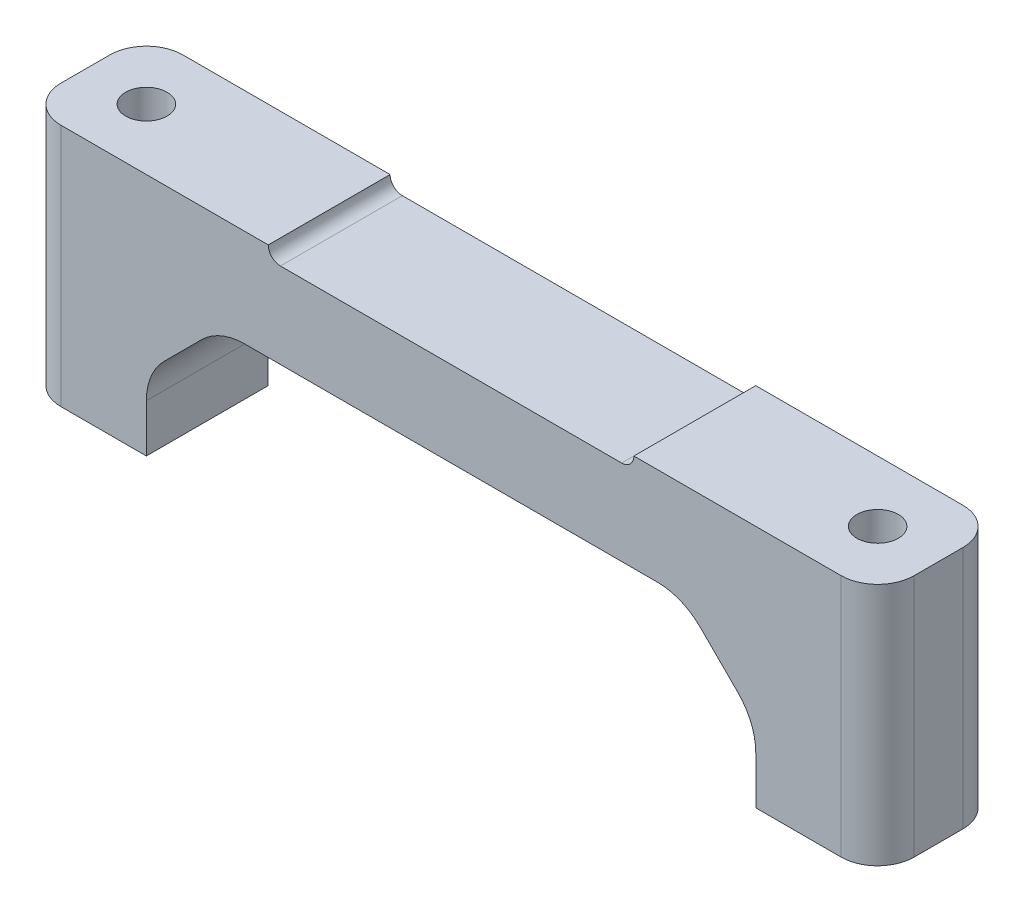
SolidWorks part; units mm, degrees
ref_plane "前视" through (0, 0, 0) normal (0, 0, 1) x (1, 0, 0)
ref_plane "上视" through (0, 0, 0) normal (0, 1, 0) x (1, 0, 0)
ref_plane "右视" through (0, 0, 0) normal (1, 0, 0) x (0, 0, -1)
sketch "草图1" plane through (0, 0, 0) normal (0, 1, 0) x (1, 0, 0)
  line L1 (-35, -5) -> (35, -5)
  line L2 (-35, -5) -> (-35, 5)
  line L3 (-35, 5) -> (35, 5)
  line L4 (35, -5) -> (35, 5)
  line L5 (-35, -5) -> (35, 5) construction
  line L6 (-35, 5) -> (35, -5) construction
  point P0 (0, 0)
  dimension "D1" = 70
  dimension "D2" = 10
extrude "凸台-拉伸1" add sketch "草图1" along normal blind 20
sketch "草图2" plane through (0, 20, 0) normal (0, 1, 0) x (1, 0, 0)
  line L0 (-35, 5) -> (-35, -5) construction
  line L1 (0, 3.006) -> (0, -1.9506) construction
  circle A0 centre (-30, 0) radius 1.7
  circle A1 centre (30, 0) radius 1.7
  dimension "D1" = 5
  dimension "D2" = 3.4
extrude "切除-拉伸1" cut sketch "草图2" against normal blind 20
sketch "草图3" plane through (0, 0, 5) normal (0, 0, 1) x (1, 0, 0)
  line L0 (-35, 0) -> (35, 0) construction
  line L1 (-25, 0) -> (25, 0)
  line L2 (-25, 0) -> (-25, 6)
  line L3 (-19, 12) -> (19, 12)
  line L4 (25, 0) -> (25, 6)
  line L5 (-25, 0) -> (25, 12) construction
  line L6 (-25, 12) -> (25, 0) construction
  line L7 (-25, 6) -> (-19, 12)
  line L8 (25, 6) -> (19, 12)
  line L9 (-35, 20) -> (35, 20) construction
  line L10 (-15, 20) -> (15, 20)
  line L11 (-15, 20) -> (-15, 19)
  line L12 (-15, 19) -> (15, 19)
  line L13 (15, 20) -> (15, 19)
  line L14 (-15, 20) -> (15, 19) construction
  line L15 (-15, 19) -> (15, 20) construction
  point P0 (0, 6)
  point P8 (0, 0)
  point P12 (0, 19.5)
  dimension "D1" = 50
  dimension "D2" = 0
  dimension "D3" = 12
  dimension "D4" = 6
  dimension "D5" = 6
  dimension "D6" = 1
  dimension "D7" = 30
extrude "切除-拉伸2" cut sketch "草图3" against normal blind 10
fillet "圆角1" radius 5 4 edges at (25, 6, 0) (19, 12, 0) (-25, 6, 0) (-19, 12, 0)
fillet "圆角2" radius 3 4 edges at (35, 10, 5) (35, 10, -5) (-35, 10, -5) (-35, 10, 5)
fillet "圆角3" radius 1 2 edges at (15, 19, 0) (-15, 19, 0)
